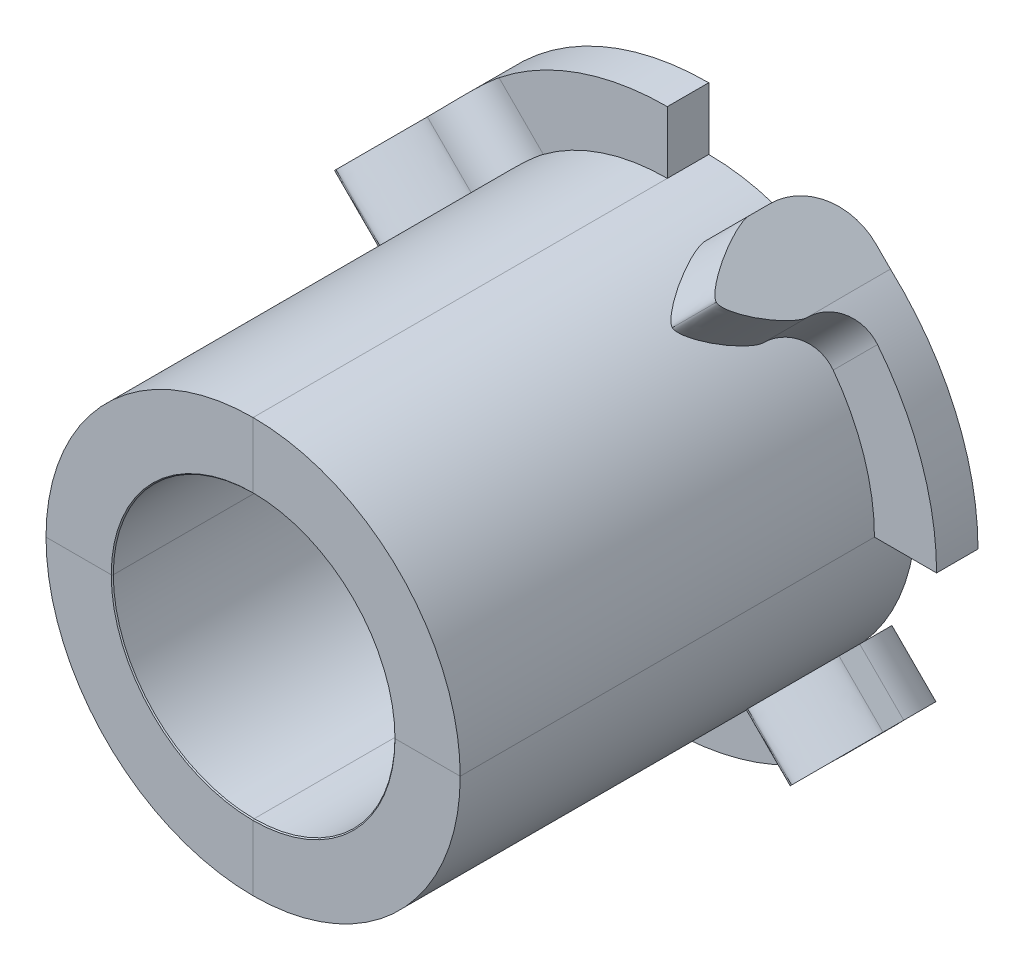
SolidWorks part; units mm, degrees
ref_plane "Front Plane" through (0, 0, 0) normal (0, 0, 1) x (1, 0, 0)
ref_plane "Top Plane" through (0, 0, 0) normal (0, 1, 0) x (1, 0, 0)
ref_plane "Right Plane" through (0, 0, 0) normal (1, 0, 0) x (0, 0, -1)
sketch "Sketch1" plane through (0, 0, 0) normal (0, 0, 1) x (1, 0, 0)
  line L0 (0, 0) -> (0, 4) construction
  line L1 (0, 0) -> (-4, 0) construction
  line L2 (-4, 0) -> (-5, 0)
  line L3 (0, 4) -> (0, 5)
  line L4 (-5, 0) -> (-6.5, 0)
  line L5 (0, 5) -> (0, 6.5)
  line L6 (-4.486, 2.2081) -> (-5.7845, 2.9648) construction
  line L7 (-3.738, 3.3207) -> (-4.8001, 4.3828)
  arc A0 (-4, 0) -> (0, 4) centre (0, 0) cw
  arc A1 (-5, 0) -> (0, 5) centre (0, 0) cw
  arc A2 (-6.5, 0) -> (0, 6.5) centre (0, 0) cw
  dimension "D1" = 4
  dimension "D2" = 5
  dimension "D3" = 6.5
  dimension "D4" = 1.5028
  dimension "D5" = 4.486
  dimension "D6" = 1.502
  dimension "D7" = 3.738
extrude "Boss-Extrude1" add sketch "Sketch1" along normal blind 1 contours A2 L4 A1 L5 region at (-2.2799, 5.1297, 0)
sketch "Sketch7" plane through (0, 0, 0) normal (0, 0, 1) x (1, 0, 0)
  line L0 (0, 0) -> (0, 4)
  line L1 (0, 0) -> (-4, 0)
  line L2 (-4, 0) -> (-5, 0)
  line L3 (0, 4) -> (0, 5)
  line L4 (-5, 0) -> (-6.5, 0)
  line L5 (0, 5) -> (0, 6.5)
  line L6 (-4.486, 2.2081) -> (-5.7845, 2.9648)
  arc A0 (-4, 0) -> (0, 4) centre (0, 0) cw
  arc A1 (-5, 0) -> (0, 5) centre (0, 0) cw
  arc A2 (-6.5, 0) -> (0, 6.5) centre (0, 0) cw
  point P2 (0, 0)
  point P11 (0, 0)
  dimension "D1" = 4
  dimension "D2" = 5
  dimension "D3" = 6.5
  dimension "D4" = 1.5028
  dimension "D5" = 4.486
extrude "Boss-Extrude4" add sketch "Sketch7" along normal blind 11 contours A1 L2 A0 L3 | A0 L1 L0 region at (-1.6977, 1.6977, 0) region at (-2.8766, 2.8766, 0)
ref_plane "Plane1" through (0, 0, 0) normal (0, 0, 1) x (-0.7071, 0.7071, 0)
sketch "Sketch3" plane through (0, 0, 0) normal (0, 0, 1) x (-0.7071, 0.7071, 0)
  line L12 (4.9913, 0.2851) -> (4.9913, 2.2851)
  line L13 (6.4933, 0.2851) -> (6.4933, 2.2851)
  line L14 (4.9913, 2.2851) -> (6.4933, 2.2851)
  line L15 (4.9913, 0.2851) -> (6.4933, 0.2851)
  line L16 (4.9913, 0.2851) -> (6.4933, 2.2851) construction
  line L17 (4.9913, 0.2951) -> (6.4933, 0.2951) construction
  point P0 (0, 0)
  dimension "D1" = 2
  dimension "D2" = 0.01
  dimension "D3" = 1.502
extrude "Boss-Extrude3" add sketch "Sketch3" along normal blind 3.5
fillet "Fillet3" radius 1.5 1 edges at (-5.6762, 2.4446, 0)
fillet "Fillet4" radius 1.5 2 edges at (-4.2622, 3.859, 3.5) (-5.6762, 2.4446, 3.5) second distance 1 conic rho 0.2 first distance on face at (-4.3958, 3.9909, 2.5625) first distance on face at (-5.6762, 2.4446, 2.5)
fillet "Fillet6" radius 1 1 edges
pattern_circular "CirPattern3" count 4 over 360 about axis through (0, 0, 11) along (0, 0, -1) of bodies 103 116
hole_wizard "Tap Drill for M8 Tap2" positions "Sketch8" profile "Sketch9" hole size "M8" standard "ISO" end condition through all
sketch "Sketch8" plane through (0, 0, 11) normal (0, 0, 1) x (1, 0, 0)
  point P0 (0, 0)
sketch "Sketch9" plane through (0, 0, 11) normal (1, 0, 0) x (0, -1, 0)
  line L0 (0, 0) -> (0, 11.075)
  line L1 (0, 11.075) -> (3.4, 11.075)
  line L2 (3.4, 11.075) -> (3.4, 0.025)
  line L3 (3.4, 0.025) -> (3.425, 0)
  line L5 (3.425, 0) -> (0, 0)
  line L6 (-3.4, 0.025) -> (-3.425, 0) construction
  line L11 (0, -6.35) -> (0, 107.95) construction
  dimension "Thru Hole Dia." = 6.8
  dimension "Thru Hole Depth" = 11.075
  dimension "Near C'Sink Dia." = 6.85
  dimension "Near C'Sink Angle" = 90
cosmetic thread "Cosmetic Thread22" parameters "D2"=8
cosmetic thread "Cosmetic Thread23" parameters "D2"=8
cosmetic thread "Cosmetic Thread24" parameters "D2"=8
cosmetic thread "Cosmetic Thread25" parameters "D2"=8
